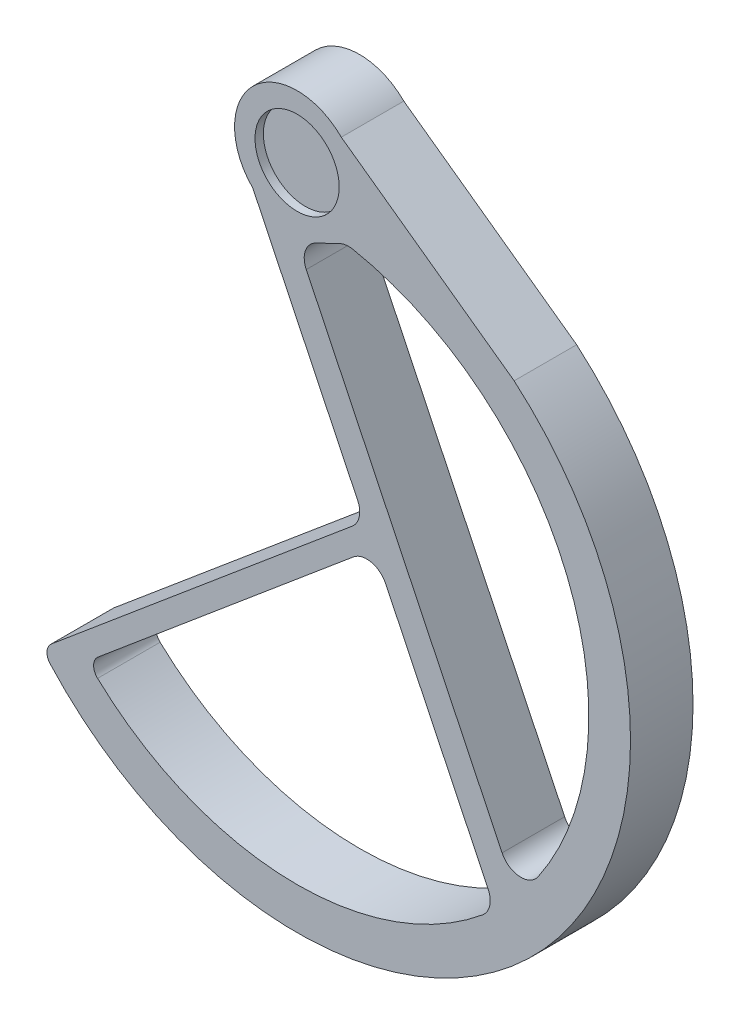
SolidWorks part; units mm, degrees
material "ABS"
ref_plane "正面" through (0, 0, 0) normal (0, 0, 1) x (1, 0, 0)
ref_plane "平面" through (0, 0, 0) normal (0, 1, 0) x (1, 0, 0)
ref_plane "右側面" through (0, 0, 0) normal (1, 0, 0) x (0, 0, -1)
sketch "ｽｹｯﾁ4" plane through (0, 0, 0) normal (0, 0, 1) x (1, 0, 0)
  line L0 (0, 0.7897) -> (0, 0)
  line L1 (-53.6231, -124.9951) -> (-58.9406, -129.4571)
  line L3 (-10.6066, -10.6066) -> (14.5363, -62.8896)
  line L4 (-53.6231, -124.9951) -> (13.2442, -68.8868)
  line L5 (21.2324, -76.8138) -> (45.8448, -127.9938)
  line L6 (10.6066, 10.6066) -> (52.0762, -19.2705)
  line L7 (-58.0696, -135.2532) -> (-57.9498, -135.1527)
  line L8 (-47.7477, -126.5866) -> (13.5112, -75.1515)
  arc A1 (-59.2335, -133.7716) -> (52.0762, -19.2705) centre (0, -80) ccw
  arc A2 (-47.8702, -131.073) -> (44.5187, -134.0193) centre (0, -80) ccw
  arc A3 (10.6066, 10.6066) -> (-10.6066, -10.6066) centre (0, 0) ccw
  arc A4 (-59.2335, -133.7716) -> (-58.9406, -129.4571) centre (-57.0123, -131.7552) cw
  arc A5 (-47.8702, -131.073) -> (-47.7477, -126.5866) centre (-45.8186, -128.8841) cw
  arc A6 (13.5112, -75.1515) -> (21.2324, -76.8138) centre (16.7264, -78.9807) cw
  arc A7 (13.2442, -68.8868) -> (14.5363, -62.8896) centre (10.0302, -65.0566) ccw
  arc A8 (45.8448, -127.9938) -> (44.5187, -134.0193) centre (41.3388, -130.1608) cw
  point P18 (-61.2836, -131.423)
  point P21 (-50.2744, -128.7081)
  point P24 (18.4421, -71.0114)
  dimension "D3" = 140
  dimension "D4" = 30
  dimension "D5" = 5
  dimension "D6" = 3
  dimension "D7" = 3
  dimension "D8" = 5
  dimension "D9" = 5
  dimension "D10" = 5
  dimension "D2" = 5
extrude "ﾎﾞｽ - 押し出し1" add sketch "ｽｹｯﾁ4" along normal blind 15 contours A7 L4 L1 A4 A1 L6 A3 L3 L5 A8 A2 A5 L8 A6 region at (29.7837, -70.5076, 0)
sketch "ｽｹｯﾁ6" plane through (0, 0, 15) normal (0, 0, 1) x (1, 0, 0)
  line L6 (49.1896, -118.7973) -> (2.2018, -21.089)
  line L7 (6.4834, -13.4819) -> (4.5408, -14.416)
  line L8 (6.4834, -13.4819) -> (10.2197, -11.6851)
  arc A0 (57.8261, -119.448) -> (13.3394, -11.2828) centre (0, -80) ccw
  arc A1 (2.2018, -21.089) -> (4.5408, -14.416) centre (6.7078, -18.9221) cw
  arc A2 (13.3394, -11.2828) -> (10.2197, -11.6851) centre (12.3866, -16.1911) ccw
  arc A3 (57.8261, -119.448) -> (49.1896, -118.7973) centre (53.6956, -116.6303) cw
  point P7 (0.0348, -16.583)
  point P14 (52.6925, -126.0814)
  dimension "D3" = 121.502
  dimension "D4" = 70
  dimension "D1" = 5
  dimension "D2" = 5
  dimension "D5" = 5
  dimension "D6" = 90
extrude "ｶｯﾄ - 押し出し1" cut sketch "ｽｹｯﾁ6" against normal blind 15
sketch "ｽｹｯﾁ7" plane through (0, 0, 15) normal (0, 0, 1) x (1, 0, 0)
  circle A0 centre (0, 0) radius 10.1
extrude "ｶｯﾄ - 押し出し2" cut sketch "ｽｹｯﾁ7" against normal blind 2
